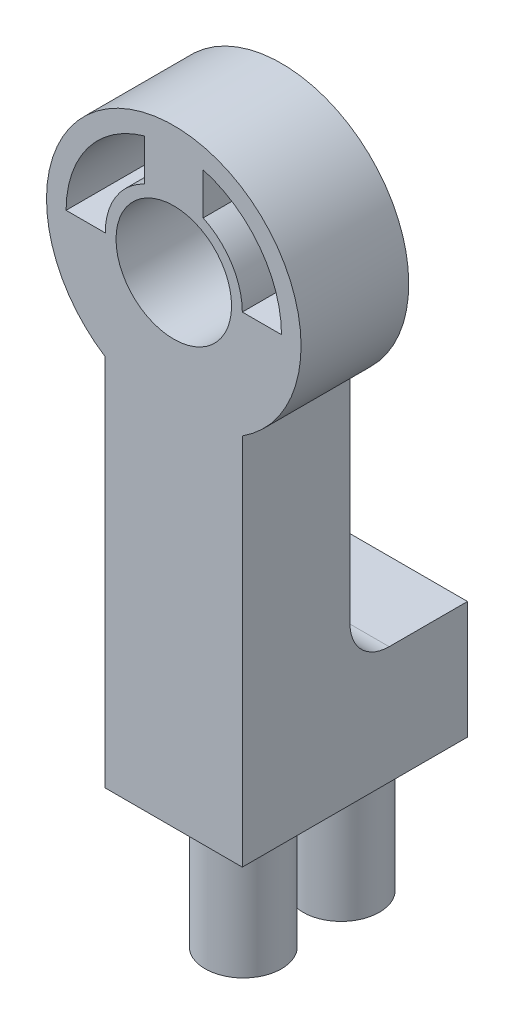
SolidWorks part; units mm, degrees
ref_plane "Front Plane" through (0, 0, 0) normal (0, 0, 1) x (1, 0, 0)
ref_plane "Top Plane" through (0, 0, 0) normal (0, 1, 0) x (1, 0, 0)
ref_plane "Right Plane" through (0, 0, 0) normal (1, 0, 0) x (0, 0, -1)
sketch "Sketch1" plane through (0, 0, 0) normal (0, 0, 1) x (1, 0, 0)
  line L0 (0, 0) -> (0, -35) construction
  line L1 (-3.5, 0) -> (-5.5, 0)
  line L2 (3.5, 0) -> (5.5, 0)
  line L3 (0, -17.5) -> (10.3868, -17.5) construction
  line L5 (-1.5, 3.1623) -> (-1.5, 5.2915)
  line L7 (1.5, 3.1623) -> (1.5, 5.2915)
  line L8 (1.5, -38.1623) -> (1.5, -40.2915)
  line L9 (-1.5, -38.1623) -> (-1.5, -40.2915)
  line L10 (3.5, -35) -> (5.5, -35)
  line L11 (-3.5, -35) -> (-5.5, -35)
  line L13 (-3.5, 0) -> (3.5, 0)
  line L14 (-3.5, 0) -> (-3.5, -35)
  line L15 (-3.5, -35) -> (3.5, -35)
  line L16 (3.5, 0) -> (3.5, -35)
  circle A0 centre (0, 0) radius 2.95
  circle A1 centre (0, 0) radius 6.5
  circle A2 centre (0, 0) radius 3.5
  circle A3 centre (0, 0) radius 5.5
  circle A4 centre (0, -35) radius 5.5
  circle A5 centre (0, -35) radius 3.5
  circle A6 centre (0, -35) radius 6.5
  circle A7 centre (0, -35) radius 2.95
  dimension "D1" = 5.9
  dimension "D2" = 13
  dimension "D3" = 11
  dimension "D4" = 7
  dimension "D5" = 35
extrude "Boss-Extrude1" add sketch "Sketch1" along normal blind 3.7 contours L14 A6 L16 A1 | A3 L16 A1 L14 | L14 A3 L16 A2 | A3 L14 A1 L16 | A6 L14 A4 L16 | A6 L16 A4 L14 | L14 A5 L16 A4 | A4 L11 L14 | A4 L16 L10 | L15 A7 A5 | L15 A7 A5 | L7 A3 L5 A2 | L1 A3 L14 | L16 A3 L2 | L13 A2 A0 | L13 A2 A0 | L8 A5 L9 A4 region at (-4.3139, -1.6382, 0) region at (-2.8919, 1.829, 0) region at (0, -3.8245, 0) region at (-3.225, -0.0783, 0) region at (-5.1348, -2.4206, 0) region at (0, -5.6156, 0) region at (0, 4.4089, 0) region at (4.3139, -1.6382, 0) region at (0, -17.5, 0) region at (0, -29.3844, 0) region at (-3.6768, -30.1401, 0) region at (0, -31.1755, 0) region at (-4.3139, -33.3618, 0) region at (0, -31.5783, 0) region at (-3.225, -35.0783, 0) region at (4.3139, -33.3618, 0) region at (0, -39.4089, 0)
sketch "Sketch2" plane through (0, 0, 0) normal (1, 0, 0) x (0, 0, -1)
  line L0 (0, 0) -> (0, -24.55) construction
  line L1 (0, -5.4772) -> (0, -29.5228) construction
  line L2 (-3.7, -5.4772) -> (-3.7, -29.5228) construction
  line L3 (-3.7, -24.55) -> (-3.1, -24.55)
  line L4 (-3.7, -24.55) -> (-3.7, -41.5)
  line L5 (-3.7, -41.5) -> (-3.1, -41.5)
  line L6 (-3.1, -24.55) -> (-3.1, -41.5)
  line L7 (-3.7, -41.5) -> (0, -41.5) construction
  dimension "D1" = 24.55
  dimension "D2" = 0.6
extrude "Cut-Extrude1" cut sketch "Sketch2" against normal blind 10 and the other way blind 10
sketch "Sketch3" plane through (0, 0, 0) normal (0, 0, -1) x (-1, 0, 0)
  circle A0 centre (0, -35) radius 2.95
  circle A1 centre (0, -35) radius 1.5
  dimension "D1" = 3
extrude "Boss-Extrude2" add sketch "Sketch3" against normal blind 3.1
sketch "Sketch4" plane through (0, 0, 0) normal (0, 0, -1) x (-1, 0, 0)
  circle A0 centre (0, -35) radius 2.5
  dimension "D1" = 5
extrude "Cut-Extrude2" cut sketch "Sketch4" against normal blind 1.5
sketch "Sketch5" plane through (0, 0, 3.1) normal (0, 0, 1) x (1, 0, 0)
  line L1 (-3.5, -24.55) -> (3.5, -24.55)
  line L2 (-3.5, -24.55) -> (-3.5, -29.5228)
  line L4 (3.5, -24.55) -> (3.5, -29.5228)
  line L5 (-5.5, -35) -> (-3.5, -35)
  line L8 (-1.5, -38.1623) -> (-1.5, -40.2915)
  line L9 (5.5, -35) -> (3.5, -35)
  line L12 (1.5, -38.1623) -> (1.5, -40.2915)
  circle A0 centre (0, -35) radius 1.5
  circle A1 centre (0, -35) radius 6.5
  circle A2 centre (0, -35) radius 3.5
  arc A3 (-5.5, -35) -> (5.5, -35) centre (0, -35) ccw
  line M2 (3.5, -35) -> (5.5, -35)
  line M4 (1.5, -40.2915) -> (1.5, -38.1623)
  arc M5 (1.5, -38.1623) -> (3.5, -35) centre (0, -35) ccw
  arc M6 (-3.5, -35) -> (-1.5, -38.1623) centre (0, -35) ccw
  line M7 (-1.5, -38.1623) -> (-1.5, -40.2915)
  line M9 (-5.5, -35) -> (-3.5, -35)
  line M10 (-3.5, -24.55) -> (-3.5, -29.5228)
  line M12 (3.5, -29.5228) -> (3.5, -24.55)
  line M13 (3.5, -24.55) -> (-3.5, -24.55)
  circle M14 centre (0, -35) radius 1.5
extrude "Boss-Extrude3" add sketch "Sketch5" along normal blind 0.4 contours A1 M12 M13 M10 | A3 A2 M2 M9 | A2 M5 M6 M14 | A3 A2 M7 M4 region at (0, -26.7003, 3.1) region at (0, -28.6838, 3.1) region at (0, -31.599, 3.1) region at (0, -39.4089, 3.1)
sketch "Sketch6" plane through (0, 0, 3.7) normal (0, 0, 1) x (1, 0, 0)
  line L0 (-1.5, 5.2915) -> (-1.5, 3.1623)
  line L2 (-3.5, -5.4772) -> (-3.5, -24.55)
  line L3 (-3.5, -24.55) -> (3.5, -24.55)
  line L4 (3.5, -5.4772) -> (3.5, -24.55)
  line L5 (1.5, 5.2915) -> (1.5, 3.1623)
  line L6 (3.5, 0) -> (5.5, 0)
  line L7 (-5.5, 0) -> (-3.5, 0)
  circle A0 centre (0, 0) radius 2.95
  arc A1 (3.5, -5.4772) -> (-3.5, -5.4772) centre (0, 0) ccw
  arc A2 (-1.5, 5.2915) -> (-5.5, 0) centre (0, 0) ccw
  arc A3 (-1.5, 3.1623) -> (-3.5, 0) centre (0, 0) ccw
  arc A4 (3.5, 0) -> (1.5, 3.1623) centre (0, 0) ccw
  arc A5 (5.5, 0) -> (1.5, 5.2915) centre (0, 0) ccw
extrude "Boss-Extrude4" add sketch "Sketch6" along normal blind 2.4
sketch "Sketch7" plane through (0, 0, 0) normal (0, 0, 1) x (1, 0, 0)
  line L1 (12.005, 7.8195) -> (-10.0995, 7.8195)
  line L2 (12.005, 7.8195) -> (12.005, -42.7273)
  line L3 (12.005, -42.7273) -> (-10.0995, -42.7273)
  line L4 (-10.0995, 7.8195) -> (-10.0995, -42.7273)
extrude "Cut-Extrude3" cut sketch "Sketch7" along normal blind 0.6
sketch "Sketch8" plane through (0, 0, 3.5) normal (0, 0, 1) x (1, 0, 0)
  line L0 (-1.5, -38.1623) -> (-1.5, -40.2915)
  line L1 (-3.5, -24.55) -> (3.5, -24.55)
  line L2 (-3.5, -24.55) -> (-3.5, -29.5228)
  line L3 (-3.5, -29.5228) -> (3.5, -29.5228)
  line L4 (3.5, -24.55) -> (3.5, -29.5228)
  line L5 (1.5, -38.1623) -> (1.5, -40.2915)
  circle A0 centre (0, -35) radius 6.5
  circle A1 centre (0, -35) radius 1.5
  circle A2 centre (0, -35) radius 5.5
  circle A3 centre (0, -35) radius 3.5
  line M1 (1.5, -40.2915) -> (1.5, -38.1623)
  arc M2 (1.5, -38.1623) -> (3.5, -35) centre (0, -35) ccw
  line M3 (3.5, -35) -> (5.5, -35)
  arc M4 (5.5, -35) -> (1.5, -40.2915) centre (0, -35) cw
  line M5 (-3.5, -24.55) -> (-3.5, -29.5228)
  arc M6 (-3.5, -29.5228) -> (3.5, -29.5228) centre (0, -35) ccw
  line M7 (3.5, -29.5228) -> (3.5, -24.55)
  line M8 (3.5, -24.55) -> (-3.5, -24.55)
  arc M9 (-1.5, -40.2915) -> (-5.5, -35) centre (0, -35) cw
  line M10 (-5.5, -35) -> (-3.5, -35)
  arc M11 (-3.5, -35) -> (-1.5, -38.1623) centre (0, -35) ccw
  line M12 (-1.5, -38.1623) -> (-1.5, -40.2915)
  circle M13 centre (0, -35) radius 1.5
extrude "Boss-Extrude5" add sketch "Sketch8" along normal blind 2.6 contours A0 M7 M8 M5 | A3 M2 M11 M13 | A3 A2 L3 M3 M10 | A2 L3 M4 M9 M6 | A3 A2 M12 M1 | L3 A2 | A2 L3 A0 region at (0, -39.4089, 3.5) region at (-2.8744, -36.8179, 3.5) region at (0, -40.6768, 3.5) region at (-4.5, -34.8771, 3.5) region at (0, -29.5137, 3.5) region at (0, -29.1095, 3.5) region at (0, -26.7003, 3.5)
sketch "Sketch9" plane through (0, 0, 6.1) normal (0, 0, 1) x (1, 0, 0)
  circle A0 centre (0, -35) radius 3.5
  circle A1 centre (0, -35) radius 5.5
extrude "Boss-Extrude6" add sketch "Sketch9" against normal blind 5.5
sketch "Sketch10" plane through (0, 0, 6.1) normal (0, 0, 1) x (1, 0, 0)
  line L1 (-3.5, -31.5) -> (3.5, -31.5)
  line L2 (-3.5, -31.5) -> (-3.5, -38.5)
  line L3 (-3.5, -38.5) -> (3.5, -38.5)
  line L4 (3.5, -31.5) -> (3.5, -38.5)
  line L5 (-3.5, -31.5) -> (3.5, -38.5) construction
  line L6 (-3.5, -38.5) -> (3.5, -31.5) construction
  dimension "D2" = 7
  dimension "D3" = 7
extrude "Cut-Extrude4" cut sketch "Sketch10" against normal blind 5.5
sketch "Sketch11" plane through (0, 0, 6.1) normal (0, 0, 1) x (1, 0, 0)
  line L0 (0, 0) -> (0, -24.55) construction
  line L2 (-9.9851, -24.55) -> (10.8803, -24.55)
  line L3 (-9.9851, -24.55) -> (-9.9851, -42.3593)
  line L4 (-9.9851, -42.3593) -> (10.8803, -42.3593)
  line L5 (10.8803, -24.55) -> (10.8803, -42.3593)
  dimension "D1" = 24.55
extrude "Cut-Extrude5" cut sketch "Sketch11" against normal blind 10
sketch "Sketch12" plane through (0, -24.55, 0) normal (0, -1, 0) x (1, 0, 0)
  line L1 (-3.5, 6.1) -> (3.5, 6.1)
  line L5 (-3.5, 0.6) -> (3.5, 0.6)
  line L6 (-3.5, 0.6) -> (-3.5, -5.4)
  line L7 (-3.5, -5.4) -> (3.5, -5.4)
  line L8 (3.5, 0.6) -> (3.5, -5.4)
  line M1 (-3.5, 0.6) -> (3.5, 0.6)
  dimension "D1" = 6
extrude "Boss-Extrude7" add sketch "Sketch12" against normal blind 6 contours L8 L6 L7 M1 region at (0, -24.55, -2.4)
fillet "Fillet1" radius 2 1 edges at (0, -18.55, 0.6)
sketch "Sketch13" plane through (0, -24.55, 0) normal (0, -1, 0) x (1, 0, 0)
  line L0 (3.5, -5.4) -> (3.5, 6.1) construction
  line L1 (3.5, 6.1) -> (-3.5, 6.1) construction
  circle A0 centre (0.05, 2.6) radius 1.95
  circle A1 centre (0.05, -2.4) radius 1.95
  dimension "D1" = 3.9
  dimension "D2" = 3.45
  dimension "D3" = 3.5
  dimension "D4" = 2
extrude "Boss-Extrude8" add sketch "Sketch13" along normal blind 7
